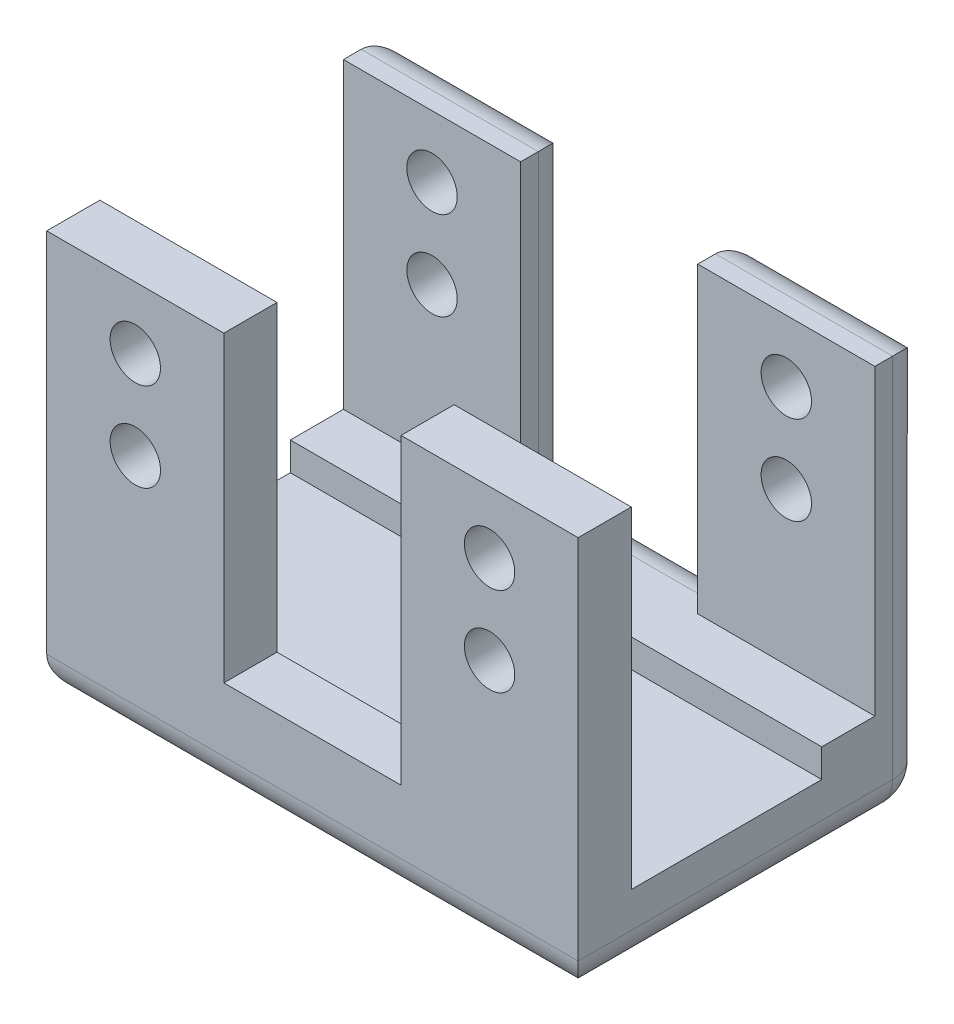
SolidWorks part; units mm, degrees
ref_plane "Front Plane" through (0, 0, 0) normal (0, 0, 1) x (1, 0, 0)
ref_plane "Top Plane" through (0, 0, 0) normal (0, 1, 0) x (1, 0, 0)
ref_plane "Right Plane" through (0, 0, 0) normal (1, 0, 0) x (0, 0, -1)
sketch "Sketch1" plane through (0, 0, 0) normal (0, 1, 0) x (1, 0, 0)
  line L1 (0, 0) -> (30, 0)
  line L2 (0, 0) -> (0, 19.75)
  line L3 (0, 19.75) -> (30, 19.75)
  line L4 (30, 0) -> (30, 19.75)
  dimension "D1" = 30
  dimension "D2" = 19.75
extrude "Boss-Extrude1" add sketch "Sketch1" along normal blind 4
sketch "Sketch2" plane through (0, 4, 0) normal (0, 1, 0) x (1, 0, 0)
  line L0 (30, 0) -> (30, 19.75) construction
  line L1 (0, 19.75) -> (30, 19.75)
  line L2 (0, 19.75) -> (0, 13.75)
  line L3 (0, 13.75) -> (30, 13.75)
  line L4 (30, 19.75) -> (30, 13.75)
  dimension "D1" = 6
extrude "Boss-Extrude2" add sketch "Sketch2" along normal blind 1.601
sketch "Sketch3" plane through (0, 4, 0) normal (0, 1, 0) x (1, 0, 0)
  line L1 (0, 0) -> (10, 0)
  line L2 (0, 0) -> (0, 3)
  line L3 (0, 3) -> (10, 3)
  line L4 (10, 0) -> (10, 3)
  line L5 (30, 0) -> (20, 0)
  line L6 (30, 0) -> (30, 3)
  line L7 (30, 3) -> (20, 3)
  line L8 (20, 0) -> (20, 3)
  dimension "D1" = 10
  dimension "D2" = 3
extrude "Boss-Extrude3" add sketch "Sketch3" along normal blind 18.7
sketch "Sketch4" plane through (0, 5.601, 0) normal (0, 1, 0) x (1, 0, 0)
  line L1 (0, 19.75) -> (10, 19.75)
  line L2 (0, 19.75) -> (0, 16.75)
  line L3 (0, 16.75) -> (10, 16.75)
  line L4 (10, 19.75) -> (10, 16.75)
  line L5 (30, 19.75) -> (20, 19.75)
  line L6 (30, 19.75) -> (30, 16.75)
  line L7 (30, 16.75) -> (20, 16.75)
  line L8 (20, 19.75) -> (20, 16.75)
  dimension "D1" = 10
  dimension "D2" = 3
extrude "Boss-Extrude4" add sketch "Sketch4" along normal blind 17.099
sketch "Sketch5" plane through (0, 4, 0) normal (0, 1, 0) x (1, 0, 0)
  line L1 (10, 3) -> (20, 3)
  line L2 (10, 3) -> (10, 0)
  line L3 (10, 0) -> (20, 0)
  line L4 (20, 3) -> (20, 0)
extrude "Boss-Extrude5" add sketch "Sketch5" along normal blind 1.601
fillet "Fillet1" radius 2 11 edges at (30, 11.35, -19.75) (25, 22.7, -19.75) (20, 14.1505, -19.75) (15, 5.601, -19.75) (10, 14.1505, -19.75) (5, 22.7, -19.75) (0, 11.35, -19.75) (15, 0, 0) (30, 0, -9.875) (15, 0, -19.75) (0, 0, -9.875)
sketch "Sketch6" plane through (0, 0, -16.75) normal (0, 0, 1) x (1, 0, 0)
  line L0 (0, 22.7) -> (10, 22.7) construction
  line L1 (5, 22.7) -> (5, 19.2) construction
  line L2 (10, 22.7) -> (20, 22.7) construction
  line L3 (15, 22.7) -> (15, 8.1156) construction
  circle A0 centre (5, 19.2) radius 1.4224
  circle A1 centre (25, 19.2) radius 1.4224
  circle A2 centre (5, 14.2) radius 1.4224
  circle A3 centre (25, 14.2) radius 1.4224
  dimension "D1" = 2.8448
  dimension "D2" = 3.5
  dimension "D3" = 2
extrude "Cut-Extrude1" cut sketch "Sketch6" against normal up to next
sketch "Sketch7" plane through (0, 0, -3) normal (0, 0, -1) x (-1, 0, 0)
  line L0 (-30, 22.7) -> (-20, 22.7) construction
  line L1 (-25, 22.7) -> (-25, 19.2) construction
  line L2 (-20, 22.7) -> (-10, 22.7) construction
  line L3 (-15, 22.7) -> (-15, 17.7883) construction
  circle A0 centre (-25, 19.2) radius 1.4224
  circle A1 centre (-5, 19.2) radius 1.4224
  circle A2 centre (-5, 14.2) radius 1.4224
  circle A3 centre (-25, 14.2) radius 1.4224
  dimension "D2" = 2.8448
  dimension "D1" = 3.5
  dimension "D3" = 2
extrude "Cut-Extrude2" cut sketch "Sketch7" against normal up to next
